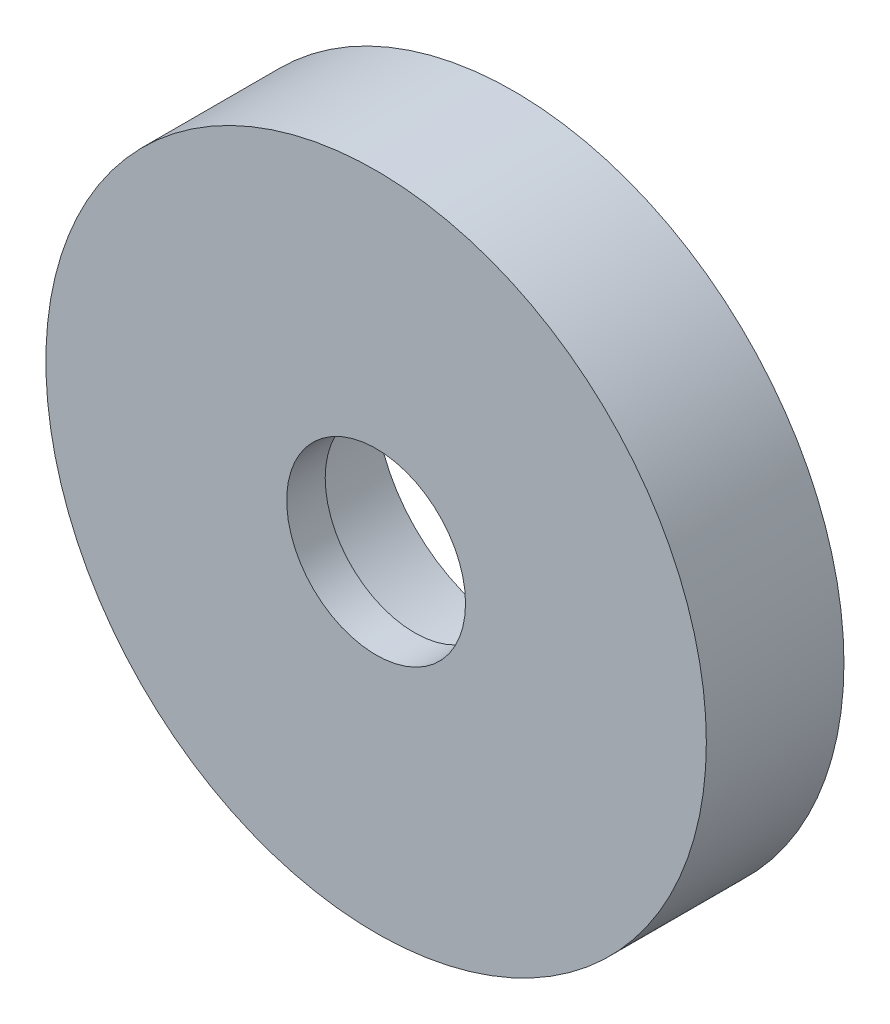
SolidWorks part; units mm, degrees
material "ABS"
ref_plane "Front Plane" through (0, 0, 0) normal (0, 0, 1) x (1, 0, 0)
ref_plane "Top Plane" through (0, 0, 0) normal (0, 1, 0) x (1, 0, 0)
ref_plane "Right Plane" through (0, 0, 0) normal (1, 0, 0) x (0, 0, -1)
sketch "Sketch1" plane through (0, 0, 0) normal (0, 0, 1) x (1, 0, 0)
  circle A0 centre (95.8641, 45.4656) radius 8.001
  circle A1 centre (95.8641, 45.4656) radius 19.05
  dimension "D1" = 16.002
  dimension "D2" = 38.1
extrude "Boss-Extrude1" add sketch "Sketch1" against normal blind 3.175
sketch "Sketch2" plane through (0, 0, 0) normal (0, 0, 1) x (1, 0, 0)
  circle A0 centre (95.8641, 45.4656) radius 19.05 construction
  circle A1 centre (95.8641, 45.4656) radius 19.05
extrude "Boss-Extrude2" add sketch "Sketch2" along normal blind 4.7625
hole_wizard "3/8 Clearance Hole1" positions "Sketch5" profile "Sketch3" hole size "3/8" standard "ANSI Inch" end condition through all
sketch "Sketch5" plane through (0, 0, 4.7625) normal (0, 0, 1) x (1, 0, 0)
  point P0 (95.8641, 45.4656)
sketch "Sketch3" plane through (95.8641, 45.4656, 4.7625) normal (1, 0, 0) x (0, -1, 0)
  line L0 (0, 0) -> (0, 7.9375)
  line L1 (0, 7.9375) -> (5.1587, 7.9375)
  line L2 (5.1587, 7.9375) -> (5.1587, 0)
  line L5 (5.1587, 0) -> (0, 0)
  line L11 (0, -6.35) -> (0, 107.95) construction
  dimension "Thru Hole Dia." = 10.3175
  dimension "Thru Hole Depth" = 7.9375
sketch "Sketch6" plane through (0, 0, 0) normal (0, 0, -1) x (-1, 0, 0)
  circle A0 centre (-95.8641, 45.4656) radius 8.001
  dimension "D1" = 16.002
extrude "Cut-Extrude1" cut sketch "Sketch6" against normal blind 2.54
